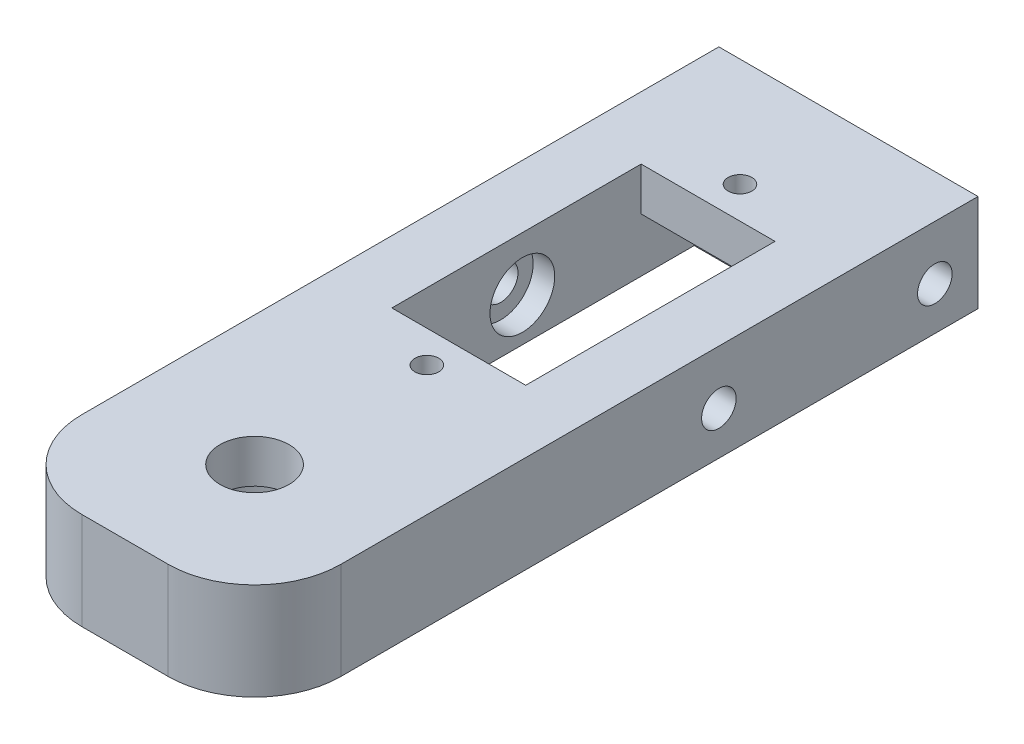
SolidWorks part; units mm, degrees
ref_plane "前视基准面" through (0, 0, 0) normal (0, 0, 1) x (1, 0, 0)
ref_plane "上视基准面" through (0, 0, 0) normal (0, 1, 0) x (1, 0, 0)
ref_plane "右视基准面" through (0, 0, 0) normal (1, 0, 0) x (0, 0, -1)
sketch "草图1" plane through (0, 0, 0) normal (1, 0, 0) x (0, 0, -1)
  line L1 (55, -4) -> (-12, -4)
  line L2 (55, -4) -> (55, 5)
  line L3 (55, 5) -> (-12, 5)
  line L4 (-12, -4) -> (-12, 5)
  line L5 (55, -4) -> (-12, 5) construction
  line L6 (55, 5) -> (-12, -4) construction
  point P0 (21.5, 0.5)
extrude "凸台-拉伸1" add sketch "草图1" along normal mid plane 24
sketch "草图2" plane through (0, -4, 0) normal (0, 1, 0) x (1, 0, 0)
  circle A0 centre (0, 0) radius 6.7
extrude "切除-拉伸1" cut sketch "草图2" along normal blind 5
sketch "草图4" plane through (0, 1, 0) normal (0, -1, 0) x (1, 0, 0)
  circle A0 centre (0, 0) radius 3.2
extrude "切除-拉伸3" cut sketch "草图4" against normal through all
sketch "草图3" plane through (0, 5, 0) normal (0, 1, 0) x (1, 0, 0)
  line L1 (6.2, 42) -> (-6.2, 42)
  line L2 (6.2, 42) -> (6.2, 18.9147)
  line L3 (6.2, 18.9147) -> (-6.2, 18.9147)
  line L4 (-6.2, 42) -> (-6.2, 18.9147)
  line L5 (6.2, 42) -> (-6.2, 18.9147) construction
  line L6 (6.2, 18.9147) -> (-6.2, 42) construction
  point P0 (0, 30.4574)
extrude "切除-拉伸2" cut sketch "草图3" against normal through all
sketch "草图5" plane through (0, -4, 0) normal (0, -1, 0) x (1, 0, 0)
  line L1 (6.2, -46.9147) -> (-6.2, -46.9147)
  line L2 (6.2, -46.9147) -> (6.2, -14)
  line L3 (6.2, -14) -> (-6.2, -14)
  line L4 (-6.2, -46.9147) -> (-6.2, -14)
  line L5 (6.2, -46.9147) -> (-6.2, -14) construction
  line L6 (6.2, -14) -> (-6.2, -46.9147) construction
  line L7 (-6.2, -42) -> (-6.2, -18.9147) construction
  line L8 (-6.2, -18.9147) -> (6.2, -18.9147) construction
  point P0 (0, -30.4574)
  point P8 (-6.2, -30.4574)
  point P11 (0, -18.9147)
extrude "切除-拉伸4" cut sketch "草图5" against normal offset from surface (5 mm away) 4 up to face at (0, 5, -30.4574)
sketch "草图6" plane through (0, 1, 0) normal (0, -1, 0) x (1, 0, 0)
  line L0 (-6.2, -30.4574) -> (6.2, -30.4574) construction
  line L1 (-6.2, -46.9147) -> (-6.2, -14) construction
  line L2 (6.2, -14) -> (6.2, -46.9147) construction
  line L3 (0, -30.4574) -> (0, -15.9574) construction
  circle A0 centre (0, -15.9574) radius 1.1
  circle A2 centre (0, -44.9574) radius 1.1
extrude "切除-拉伸5" cut sketch "草图6" against normal through all
fillet "圆角1" radius 8 2 edges at (-12, 0.5, 12) (12, 0.5, 12)
sketch "草图7" plane through (12, 0, 0) normal (1, 0, 0) x (0, 0, -1)
  line L0 (31.0016, 0) -> (51.0016, 0) construction
  circle A0 centre (51.0016, 0) radius 1.6
  circle A1 centre (31.0016, 0) radius 1.6
extrude "切除-拉伸6" cut sketch "草图7" against normal through all
sketch "草图8" plane through (-6.2, 0, 0) normal (1, 0, 0) x (0, 0, -1)
  circle A0 centre (31.0016, 0) radius 3
extrude "切除-拉伸7" cut sketch "草图8" against normal blind 2
mirror "镜向1" about plane through (0, 0, 0) normal (1, 0, 0) of "切除-拉伸7"
